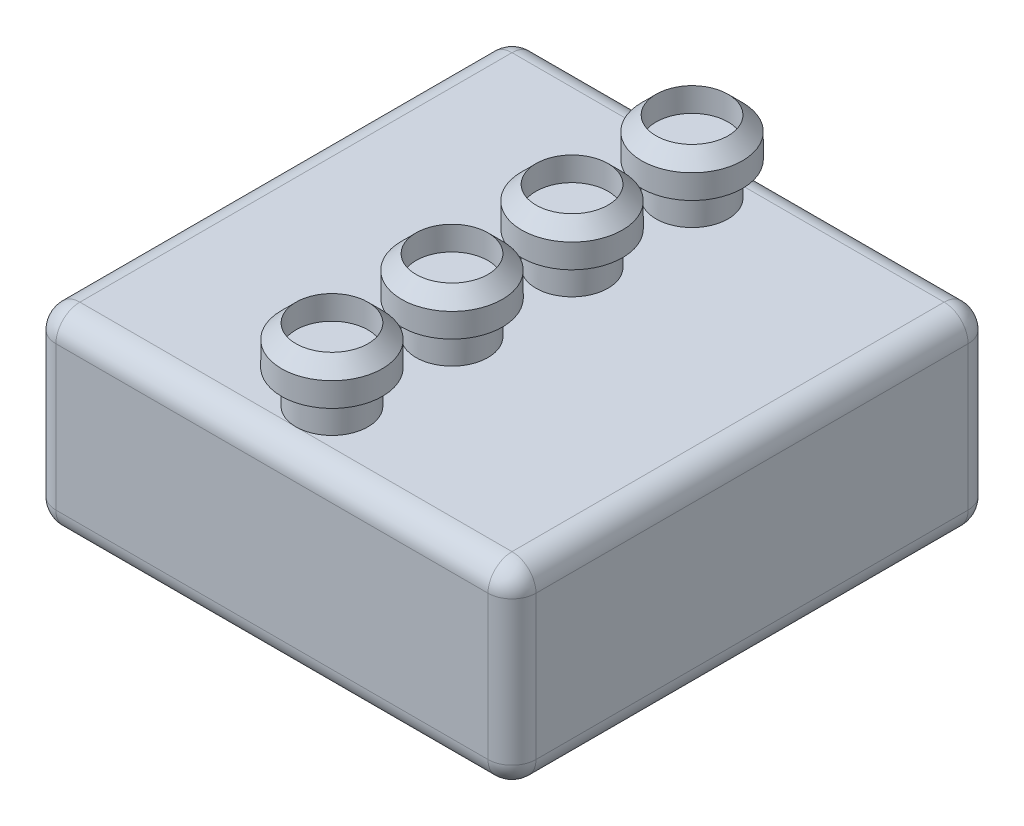
SolidWorks part; units mm, degrees
ref_plane "Front Plane" through (0, 0, 0) normal (0, 0, 1) x (1, 0, 0)
ref_plane "Top Plane" through (0, 0, 0) normal (0, 1, 0) x (1, 0, 0)
ref_plane "Right Plane" through (0, 0, 0) normal (1, 0, 0) x (0, 0, -1)
sketch "Sketch1" plane through (0, 0, 0) normal (0, 1, 0) x (1, 0, 0)
  line L1 (-50, -50) -> (50, -50)
  line L2 (-50, -50) -> (-50, 50)
  line L3 (-50, 50) -> (50, 50)
  line L4 (50, -50) -> (50, 50)
  line L5 (-50, -50) -> (50, 50) construction
  line L6 (-50, 50) -> (50, -50) construction
  point P0 (0, 0)
  dimension "D1" = 100
  dimension "D2" = 100
extrude "Boss-Extrude1" add sketch "Sketch1" along normal blind 40
sketch "Sketch2" plane through (0, 40, 0) normal (0, 1, 0) x (1, 0, 0)
  line L0 (0, -37.5) -> (0, 37.5) construction
  line L1 (0, 37.5) -> (0, 50) construction
  line L2 (50, 50) -> (-50, 50) construction
  line L3 (0, -37.5) -> (0, -50) construction
  line L4 (-50, -50) -> (50, -50) construction
  circle A0 centre (0, -37.5) radius 10.5
  circle A1 centre (0, -37.5) radius 7.5
  circle A2 centre (0, -12.5) radius 10.5
  circle A3 centre (0, -12.5) radius 7.5
  circle A4 centre (0, 12.5) radius 10.5
  circle A5 centre (0, 12.5) radius 7.5
  circle A6 centre (0, 37.5) radius 10.5
  circle A7 centre (0, 37.5) radius 7.5
  dimension "D1" = 21
  dimension "D2" = 15
  dimension "D3" = 4
extrude "Boss-Extrude2" add sketch "Sketch2" along normal blind 10 contours A1 | A3 | A5 | A7 region at (0, 40, 37.5) region at (0, 40, 12.5) region at (0, 40, -12.5) region at (0, 40, -37.5)
extrude "Boss-Extrude3" add sketch "Sketch2<4>" along normal blind 10 from offset 7
sketch "Sketch2<4>" plane through (0, 40, 0) normal (0, 1, 0) x (1, 0, 0) same geometry as "Sketch2"
chamfer "Chamfer1" distance 1 angle 45 4 edges at (0, 47, -30) (0, 47, -5) (0, 47, 20) (0, 47, 45)
chamfer "Chamfer2" distance 5 angle 45 4 edges at (0, 57, -27) (0, 57, -2) (0, 57, 23) (0, 57, 48)
fillet "Fillet1" radius 5 12 edges at (0, 40, 50) (0, 0, 50) (-50, 40, 0) (-50, 20, 50) (-50, 0, 0) (0, 40, -50) (-50, 20, -50) (0, 0, -50) (50, 20, 50) (50, 40, 0) (50, 20, -50) (50, 0, 0)
